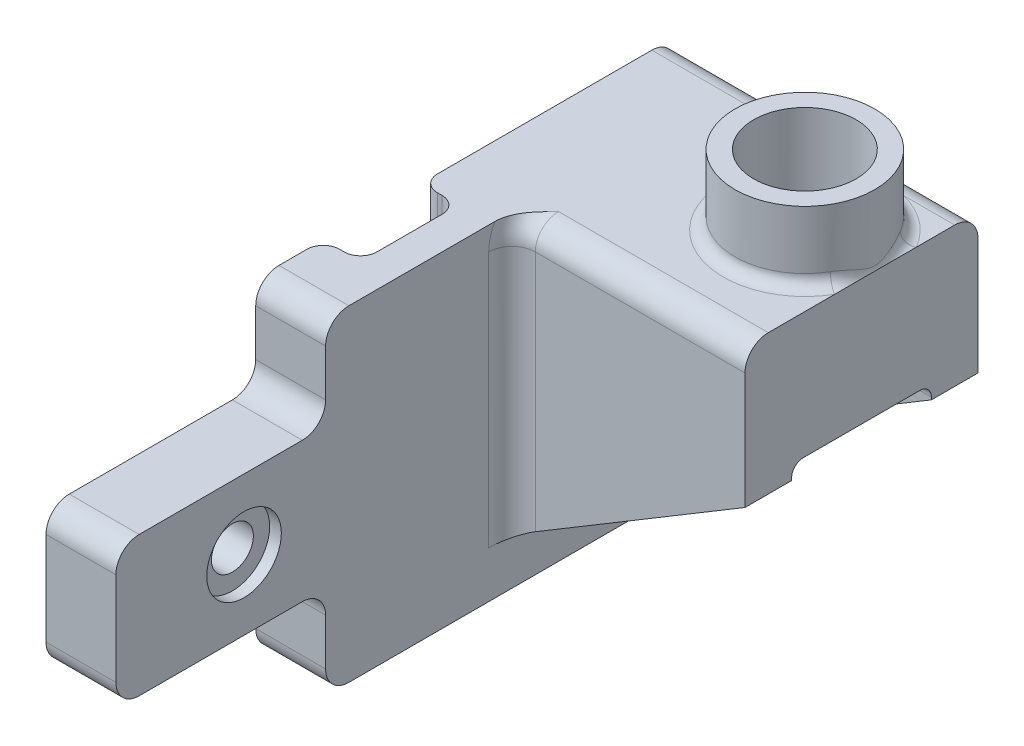
SolidWorks part; units mm, degrees
ref_plane "Front Plane" through (0, 0, 0) normal (0, 0, 1) x (1, 0, 0)
ref_plane "Top Plane" through (0, 0, 0) normal (0, 1, 0) x (1, 0, 0)
ref_plane "Right Plane" through (0, 0, 0) normal (1, 0, 0) x (0, 0, -1)
sketch "Sketch1" plane through (0, 0, 0) normal (1, 0, 0) x (0, 0, -1)
  line L1 (-68.2378, -29.504) -> (-40.2378, -29.504)
  line L2 (-68.2378, -29.504) -> (-68.2378, -35.504)
  line L3 (-68.2378, -35.504) -> (-40.2378, -35.504)
  line L4 (-40.2378, -29.504) -> (-40.2378, -35.504)
  dimension "D1" = 28
  dimension "D2" = 6
extrude "Boss-Extrude1" add sketch "Sketch1" along normal blind 3
sketch "Sketch4" plane through (3, 0, 0) normal (1, 0, 0) x (0, 0, -1)
  line L0 (-68.2378, -29.504) -> (-68.2378, -35.504) construction
  line L1 (-59.2378, -25.504) -> (-41.2378, -25.504)
  line L2 (-59.2378, -25.504) -> (-59.2378, -39.504)
  line L3 (-59.2378, -39.504) -> (-41.2378, -39.504)
  line L4 (-41.2378, -25.504) -> (-41.2378, -39.504)
  line L5 (-40.2378, -35.504) -> (-40.2378, -29.504) construction
  line L6 (-40.2378, -29.504) -> (-68.2378, -29.504) construction
  line L7 (-68.2378, -35.504) -> (-40.2378, -35.504) construction
  dimension "D1" = 9
  dimension "D2" = 1
  dimension "D3" = 4
  dimension "D4" = 4
extrude "Boss-Extrude2" add sketch "Sketch4" against normal blind 3
sketch "Sketch2" plane through (3, 0, 0) normal (1, 0, 0) x (0, 0, -1)
  line L0 (-40.2378, -29.504) -> (-41.2378, -29.504) construction
  line L1 (-68.2378, -29.504) -> (-68.2378, -35.504) construction
  line L2 (-40.2378, -35.504) -> (-40.2378, -29.504) construction
  circle A0 centre (-62.7378, -32.504) radius 0.9
  circle A1 centre (-45.7378, -32.504) radius 0.9
  dimension "D1" = 3
  dimension "D2" = 3
  dimension "D3" = 5.5
  dimension "D4" = 5.5
  dimension "D5" = 1.8
  dimension "D6" = 1.8
extrude "Cut-Extrude1" cut sketch "Sketch2" against normal blind 3
sketch "Sketch3" plane through (3, 0, 0) normal (1, 0, 0) x (0, 0, -1)
  circle A0 centre (-62.7378, -32.504) radius 1.6
  circle A1 centre (-45.7378, -32.504) radius 1.6
  dimension "D1" = 3.2
  dimension "D2" = 3.2
extrude "Cut-Extrude2" cut sketch "Sketch3" against normal blind 0.5
sketch "Sketch6" plane through (3, 0, 0) normal (1, 0, 0) x (0, 0, -1)
  line L0 (-41.2378, -25.504) -> (-59.2378, -25.504) construction
  line L1 (-41.2378, -29.504) -> (-51.2378, -29.504)
  line L2 (-41.2378, -29.504) -> (-41.2378, -25.504)
  line L3 (-41.2378, -25.504) -> (-51.2378, -25.504)
  line L4 (-51.2378, -29.504) -> (-51.2378, -25.504)
  dimension "D1" = 10
extrude "Boss-Extrude3" add sketch "Sketch6" along normal blind 10
sketch "Sketch7" plane through (3, 0, 0) normal (1, 0, 0) x (0, 0, -1)
  line L1 (-51.2378, -29.504) -> (-49.2378, -29.504)
  line L2 (-51.2378, -29.504) -> (-51.2378, -37.504)
  line L3 (-51.2378, -37.504) -> (-49.2378, -37.504)
  line L4 (-49.2378, -29.504) -> (-49.2378, -37.504)
  line L5 (-41.2378, -29.504) -> (-43.2378, -29.504)
  line L6 (-41.2378, -29.504) -> (-41.2378, -37.504)
  line L7 (-41.2378, -37.504) -> (-43.2378, -37.504)
  line L8 (-43.2378, -29.504) -> (-43.2378, -37.504)
  dimension "D1" = 8
  dimension "D2" = 8
  dimension "D3" = 2
  dimension "D4" = 2
extrude "Boss-Extrude4" add sketch "Sketch7" along normal blind 10
sketch "Sketch8" plane through (0, 0, 51.2378) normal (0, 0, 1) x (1, 0, 0)
  line L0 (13, -31.504) -> (3, -37.504)
  line L1 (13, -25.504) -> (13, -37.504) construction
  line L2 (3, -37.504) -> (13, -37.504)
  line L3 (13, -37.504) -> (13, -31.504)
  dimension "D1" = 6
extrude "Cut-Extrude4" cut sketch "Sketch8" against normal through all
sketch "Sketch9" plane through (0, -25.504, 0) normal (0, 1, 0) x (1, 0, 0)
  line L0 (0, -41.2378) -> (13, -41.2378) construction
  line L1 (13, -41.2378) -> (13, -51.2378) construction
  circle A0 centre (9.97, -45.6378) radius 2.2
  dimension "D1" = 4.4
  dimension "D2" = 3.03
  dimension "D3" = 4.4
sketch "Sketch10" plane through (13, 0, 0) normal (1, 0, 0) x (0, 0, -1)
  line L0 (-43.2378, -29.504) -> (-43.2378, -31.504) construction
  line L1 (-49.2378, -29.504) -> (-43.2378, -29.504)
  line L2 (-49.2378, -29.504) -> (-49.2378, -30.904)
  line L3 (-49.2378, -30.904) -> (-43.2378, -30.904)
  line L4 (-43.2378, -29.504) -> (-43.2378, -30.904)
  dimension "D1" = 1.4
extrude "Boss-Extrude5" add sketch "Sketch10" against normal up to surface (10 mm away) up to face at (3, -33.504, 53.095)
extrude "Cut-Extrude5" cut sketch "Sketch9" against normal blind 10 contours A0
sketch "Sketch11" plane through (3, 0, 0) normal (1, 0, 0) x (0, 0, -1)
  line L1 (-40.2378, -29.504) -> (-41.2378, -29.504)
  line L2 (-40.2378, -29.504) -> (-40.2378, -35.504)
  line L3 (-40.2378, -35.504) -> (-41.2378, -35.504)
  line L4 (-41.2378, -29.504) -> (-41.2378, -35.504)
extrude "Cut-Extrude6" cut sketch "Sketch11" against normal through all
fillet "Fillet3" radius 1 8 edges at (6.5, -25.504, 41.2378) (1.5, -39.504, 41.2378) (1.5, -39.504, 59.2378) (1.5, -35.504, 59.2378) (1.5, -35.504, 68.2378) (1.5, -29.504, 59.2378) (1.5, -29.504, 68.2378) (1.5, -25.504, 59.2378)
fillet "Fillet4" radius 1 1 edges at (8, -25.504, 51.2378)
sketch "Sketch12" plane through (0, -25.504, 0) normal (0, 1, 0) x (1, 0, 0)
  circle A0 centre (9.97, -45.6378) radius 3
  dimension "D1" = 6
extrude "Boss-Extrude6" add sketch "Sketch12" along normal blind 3
fillet "Fillet5" radius 0.5 1 edges at (9.97, -25.504, 48.6378)
sketch "Sketch13" plane through (0, -25.504, 0) normal (0, -1, 0) x (1, 0, 0)
  circle A0 centre (9.97, 45.6378) radius 2.2
extrude "Cut-Extrude7" cut sketch "Sketch13" against normal through all
fillet "Fillet6" radius 1 2 edges at (3, -25.7969, 50.9449) (3, -32.004, 51.2378)
fillet "Fillet7" radius 0.5 2 edges at (8, -30.904, 43.2378) (8, -30.904, 49.2378)
fillet "Fillet8" radius 0.5 6 edges at (3, -34.454, 49.2378) (3, -31.0504, 49.0914) (3, -30.904, 47.2378) (3, -30.904, 44.7378) (3, -31.0504, 43.3843) (3, -34.454, 43.2378)
sketch "Sketch14" plane through (0, -25.504, 0) normal (0, 1, 0) x (1, 0, 0)
  line L0 (0, -42.2378) -> (0, -58.2378) construction
  line L1 (0, -56.3378) -> (1.6, -56.3378)
  line L2 (0, -56.3378) -> (0, -52.1378)
  line L3 (0, -52.1378) -> (1.6, -52.1378)
  line L4 (1.6, -56.3378) -> (1.6, -52.1378)
  line L5 (3, -68.2378) -> (0, -68.2378) construction
  dimension "D1" = 4.2
  dimension "D2" = 1.6
  dimension "D3" = 11.9
extrude "Cut-Extrude8" cut sketch "Sketch14" against normal through all
fillet "Fillet9" radius 0.7 4 edges at (0, -32.504, 56.3378) (1.6, -32.504, 56.3378) (0, -32.504, 52.1378) (1.6, -32.504, 52.1378)
